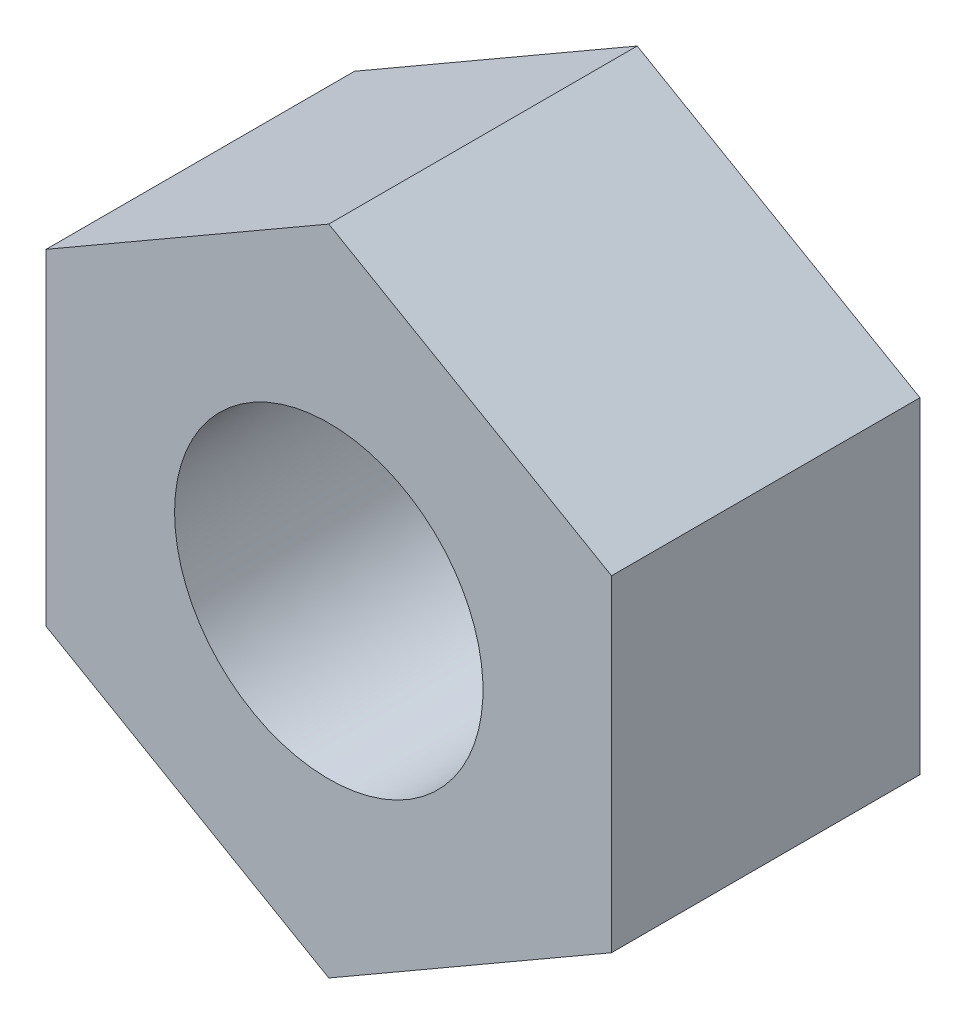
SolidWorks part; units mm, degrees
ref_plane "Front" through (0, 0, 0) normal (0, 0, 1) x (1, 0, 0)
ref_plane "Top" through (0, 0, 0) normal (0, 1, 0) x (1, 0, 0)
ref_plane "Right" through (0, 0, 0) normal (1, 0, 0) x (0, 0, -1)
sketch "Sketch1" plane through (0, 0, 0) normal (0, 0, 1) x (1, 0, 0)
  line L0 (0, 1.5) -> (0, 1) construction
  line L1 (-2.75, 1.5877) -> (-2.75, -1.5877)
  line L2 (-2.75, -1.5877) -> (0, -3.1754)
  line L3 (0, -3.1754) -> (2.75, -1.5877)
  line L4 (2.75, -1.5877) -> (2.75, 1.5877)
  line L5 (2.75, 1.5877) -> (0, 3.1754)
  line L6 (0, 3.1754) -> (-2.75, 1.5877)
  circle A0 centre (0, 0) radius 2.75 construction
  circle A1 centre (0, 0) radius 1.5 construction
  point P10 (0, 1.5)
  dimension "Width" = 5.5
  dimension "Thread Size" = 3
  dimension "Thread Pitch" = 0.5
sketch "Sketch2" plane through (0, 0, 0) normal (1, 0, 0) x (0, 0, -1)
  line L0 (-1.2, 0) -> (1.2, 0) construction
  line L1 (-1.2, 3.1754) -> (1.2, 3.1754) construction
  dimension "Height" = 2.4
sketch "Sketch15" plane through (0, 0, 0) normal (0, 0, 1) x (1, 0, 0)
  line L1 (0, 3.1754) -> (-2.75, 1.5877)
  line L2 (-2.75, 1.5877) -> (-2.75, -1.5877)
  line L3 (-2.75, -1.5877) -> (0, -3.1754)
  line L4 (0, -3.1754) -> (2.75, -1.5877)
  line L5 (2.75, -1.5877) -> (2.75, 1.5877)
  line L6 (2.75, 1.5877) -> (0, 3.1754)
  circle A0 centre (0, 0) radius 2.75 construction
extrude "Boss-Extrude2" add sketch "Sketch15" along normal mid plane 3
sketch "Sketch16" plane through (0, 0, 0) normal (0, 0, 1) x (1, 0, 0)
  circle A0 centre (0, 0) radius 1.5 construction
  circle A1 centre (0, 0) radius 1.5
sketch "Sketch4" plane through (0, 0, -1.5) normal (0, 0, -1) x (-1, 0, 0)
  circle A0 centre (0, 0) radius 1.5 construction
  circle A1 centre (0, 0) radius 1.5
extrude "Cut-Extrude4" cut sketch "Sketch16" against normal through all both and the other way through all
sketch "Sketch8" plane through (0, 0, 1.5) normal (0, 0, 1) x (1, 0, 0)
  line L0 (0.3882, -1.4489) -> (0, 0) construction
  line L2 (0, 1.5) -> (0, 1) construction
  circle A0 centre (0, 0) radius 1.5 construction
  point P0 (0.3882, -1.4489)
  dimension "D1" = 15
sketch "Sketch13" plane through (0, 0, -1.5) normal (0, 0, -1) x (-1, 0, 0)
  circle A0 centre (0, 0) radius 1.5 construction
  circle A1 centre (0, 0) radius 1.5
extrude "Boss-Extrude1" add sketch "Sketch13" against normal up to surface (3 mm away) separate body up to face at (1.5, 0, 1.5)
sketch "Sketch12" plane through (0, 0, 0) normal (1, 0, 0) x (0, 0, -1)
  line L0 (1.9375, 1.5) -> (1.5, 1.5)
  line L1 (1.9375, 1.5) -> (1.75, 1.1752)
  line L2 (1.75, 1.1752) -> (1.6875, 1.1752)
  line L3 (1.6875, 1.1752) -> (1.5, 1.5)
  line L4 (1.7188, 1.1752) -> (1.7188, 1.5) construction
  line L5 (1.5938, 1.3376) -> (1.8438, 1.3376) construction
  dimension "D1" = 60
  dimension "D2" = 0.0625
  dimension "D3" = 0.25
sketch "Sketch17" plane through (0, 0, 1.5) normal (0, 0, 1) x (1, 0, 0)
  circle A1 centre (0, 0) radius 1.5
  circle A2 centre (0, 0) radius 1.5
  dimension "D1" = 0
extrude "Boss-Extrude3" add sketch "Sketch17" against normal up to surface (3 mm away) up to face at (1.5, 0, -1.5)
combine bodies "Combine1" operation type subtract main body 127 bodies to subtract 117
equation "\"D1\"= \"Height@Sketch2\""
